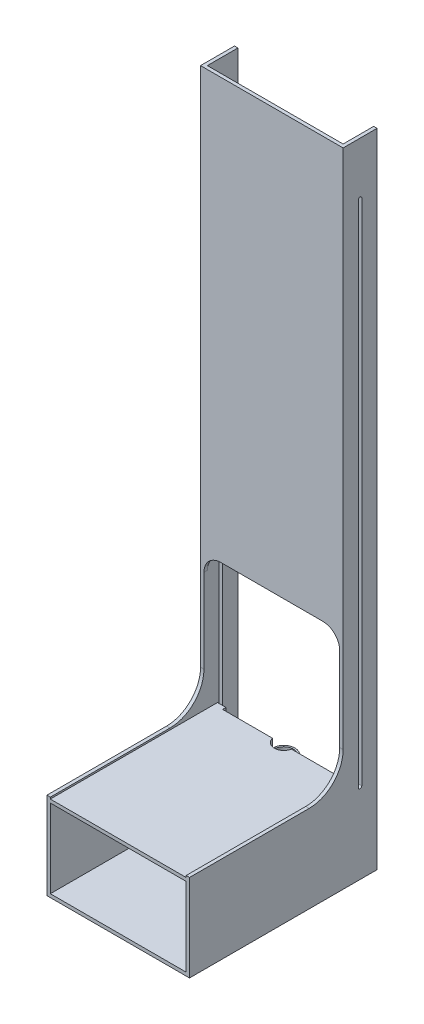
SolidWorks part; units mm, degrees
material "AISI 4340 Steel, annealed"
ref_plane "Front Plane" through (0, 0, 0) normal (0, 0, 1) x (1, 0, 0)
ref_plane "Top Plane" through (0, 0, 0) normal (0, 1, 0) x (1, 0, 0)
ref_plane "Right Plane" through (0, 0, 0) normal (1, 0, 0) x (0, 0, -1)
ref_plane "Right side of elevator platform" through (200, 0, 0) normal (1, 0, 0) x (0, 0, -1)
sketch "Sketch2" plane through (200, 0, 0) normal (1, 0, 0) x (0, 0, -1)
  line L0 (50, 236.5) -> (50, 1736.5) construction
  line L1 (45, 236.5) -> (45, 1736.5)
  line L2 (55, 236.5) -> (55, 1736.5)
  line L4 (0, 0) -> (100, 0)
  line L5 (0, 0) -> (0, 1800)
  line L6 (0, 1800) -> (100, 1800)
  line L7 (100, 0) -> (100, 1800)
  arc A0 (45, 236.5) -> (55, 236.5) centre (50, 236.5) ccw
  arc A1 (55, 1736.5) -> (45, 1736.5) centre (50, 1736.5) ccw
  point P2 (50, 986.5)
  dimension "D6" = 5
  dimension "D1" = 1800
  dimension "D2" = 100
  dimension "D3" = 50
  dimension "D4" = 236.5
  dimension "D5" = 63.5
extrude "Right side guide" add sketch "Sketch2" along normal blind 10
sketch "Sketch3" plane through (200, 0, 0) normal (-1, 0, 0) x (0, 0, 1)
  line L0 (0, 1800) -> (0, 0) construction
  line L1 (-100, 0) -> (0, 0)
  line L2 (-100, 0) -> (-100, 10)
  line L3 (-100, 10) -> (0, 10)
  line L4 (0, 0) -> (0, 10)
  dimension "D1" = 10
extrude "Bottom connection" add sketch "Sketch3" along normal blind 400
sketch "Sketch4" plane through (-200, 0, 0) normal (-1, 0, 0) x (0, 0, 1)
  line L0 (-55, 236.5) -> (-55, 1736.5) construction
  line L1 (-45, 1736.5) -> (-45, 236.5) construction
  line L2 (-55, 236.5) -> (-55, 1736.5)
  line L3 (-45, 1736.5) -> (-45, 236.5)
  line L4 (-100, 10) -> (0, 10)
  line L5 (0, 10) -> (0, 1800)
  line L6 (0, 1800) -> (-100, 1800)
  line L7 (-100, 1800) -> (-100, 10)
  line L9 (0, 10) -> (0, 1800)
  line L10 (0, 1800) -> (-100, 1800)
  line L11 (-100, 1800) -> (-100, 10)
  line L16 (-100, 10) -> (-100, 0)
  line L17 (-100, 0) -> (0, 0)
  line L18 (0, 0) -> (0, 10)
  line L19 (0, 10) -> (-100, 10)
  line L20 (-100, 10) -> (-100, 0)
  line L21 (-100, 0) -> (0, 0)
  line L22 (0, 0) -> (0, 10)
  arc A0 (-45, 1736.5) -> (-55, 1736.5) centre (-50, 1736.5) ccw construction
  arc A1 (-55, 236.5) -> (-45, 236.5) centre (-50, 236.5) ccw construction
  arc A2 (-45, 1736.5) -> (-55, 1736.5) centre (-50, 1736.5) ccw
  arc A3 (-55, 236.5) -> (-45, 236.5) centre (-50, 236.5) ccw
  dimension "D1" = 0
  dimension "D2" = 0
extrude "Left side guide" add sketch "Sketch4" along normal blind 10
sketch "Sketch5" plane through (0, 0, 0) normal (0, 0, 1) x (1, 0, 0)
  line L0 (-200, 10) -> (-200, 1800) construction
  line L1 (-200, 1800) -> (200, 1800)
  line L2 (-200, 1800) -> (-200, 653.8)
  line L3 (-200, 653.8) -> (200, 653.8)
  line L4 (200, 1800) -> (200, 653.8)
  line L5 (200, 1800) -> (200, 10) construction
  line L6 (210, 1800) -> (200, 1800) construction
  line L7 (-200, 10) -> (200, 10) construction
  dimension "D1" = 643.8
extrude "Structural webbing extrude" add sketch "Sketch5" against normal blind 10
sketch "Sketch6" plane through (0, 0, 0) normal (0, 0, 1) x (1, 0, 0)
  line L0 (-210, 251.5) -> (-210, 0)
  line L1 (-210, 0) -> (-210, 1800) construction
  line L2 (-210, 0) -> (210, 0)
  line L3 (210, 0) -> (210, 251.5)
  line L4 (210, 1800) -> (210, 0) construction
  line L5 (210, 251.5) -> (200, 251.5)
  line L6 (200, 653.8) -> (200, 10) construction
  line L7 (200, 251.5) -> (200, 10)
  line L8 (200, 10) -> (-200, 10)
  line L9 (-200, 10) -> (-200, 251.5)
  line L10 (-200, 10) -> (-200, 653.8) construction
  line L11 (-200, 251.5) -> (-210, 251.5)
  dimension "D1" = 241.5
extrude "Input roller holder extrude" add sketch "Sketch6" along normal blind 452.52
sketch "Sketch7" plane through (200, 0, 0) normal (-1, 0, 0) x (0, 0, 1)
  line L0 (0, 653.8) -> (0, 251.5) construction
  line L1 (452.52, 251.5) -> (-40, 251.5)
  line L2 (452.52, 251.5) -> (452.52, 241.5)
  line L3 (452.52, 241.5) -> (-40, 241.5)
  line L4 (-40, 251.5) -> (-40, 241.5)
  dimension "D1" = 40
  dimension "D2" = 10
extrude "Input roller platform" add sketch "Sketch7" along normal up to next
sketch "Sketch8" plane through (0, 251.5, 0) normal (0, 1, 0) x (1, 0, 0)
  line L1 (-210, -452.52) -> (-200, -452.52)
  line L2 (-210, -452.52) -> (-210, 0)
  line L3 (-210, 0) -> (-200, 0)
  line L4 (-200, -452.52) -> (-200, 0)
  line L5 (200, 0) -> (210, 0)
  line L6 (200, 0) -> (200, -452.52)
  line L7 (200, -452.52) -> (210, -452.52)
  line L8 (210, 0) -> (210, -452.52)
extrude "Siding outline" add sketch "Sketch8" along normal blind 5
sketch "Sketch9" plane through (0, 1800, 0) normal (0, 1, 0) x (1, 0, 0)
  line L8 (200, 100) -> (200, 10)
  line L9 (200, 10) -> (-200, 10)
  line L10 (-200, 10) -> (-200, 100)
  line L11 (-200, 100) -> (-210, 100)
  line L12 (-210, 100) -> (-210, 0)
  line L13 (-210, 0) -> (210, 0)
  line L14 (210, 0) -> (210, 100)
  line L15 (210, 100) -> (200, 100)
  line L16 (200, 100) -> (200, 10)
  line L17 (200, 10) -> (-200, 10)
  line L18 (-200, 10) -> (-200, 100)
  line L19 (-200, 100) -> (-210, 100)
  line L20 (-210, 100) -> (-210, 0)
  line L21 (-210, 0) -> (210, 0)
  line L22 (210, 0) -> (210, 100)
  line L23 (210, 100) -> (200, 100)
  dimension "D1" = 0
extrude "Lip to prevent box from falling out" add sketch "Sketch9" along normal blind 91.5
fillet "Vertical section fillets" radius 100 2 edges at (205, 256.5, 0) (-205, 256.5, 0)
fillet "Smaller fillets" radius 50 2 edges at (200, 653.8, -5) (-200, 653.8, -5)
sketch "Sketch11" plane through (0, 0, -40) normal (0, 0, -1) x (-1, 0, 0)
  line L0 (200, 251.5) -> (-200, 251.5) construction
  line L1 (-175, 251.5) -> (175, 251.5)
  line L2 (-175, 251.5) -> (-175, 241.5)
  line L3 (-175, 241.5) -> (175, 241.5)
  line L4 (175, 251.5) -> (175, 241.5)
  line L5 (200, 241.5) -> (-200, 241.5) construction
  line L6 (-200, 251.5) -> (-200, 241.5) construction
  line L7 (200, 251.5) -> (200, 241.5) construction
  dimension "D1" = 25
  dimension "D2" = 25
extrude "Gate spacing cut" cut sketch "Sketch11" against normal blind 10
sketch "Sketch12" plane through (-200, 0, 0) normal (1, 0, 0) x (0, 0, -1)
  line L1 (45, 221.5) -> (40, 221.5)
  line L2 (45, 221.5) -> (45, 10)
  line L3 (45, 10) -> (40, 10)
  line L4 (40, 221.5) -> (40, 10)
  line L5 (100, 1891.5) -> (100, 10) construction
  line L6 (45, 236.5) -> (45, 1736.5) construction
  line L7 (-452.52, 10) -> (100, 10) construction
  line L8 (40, 241.5) -> (-452.52, 241.5) construction
  line L9 (30, 241.5) -> (25, 241.5)
  line L10 (30, 241.5) -> (30, 10)
  line L11 (30, 10) -> (25, 10)
  line L12 (25, 241.5) -> (25, 10)
  point P17 (0, 0)
  point P18 (45, 221.5)
  point P19 (0, 0)
  point P20 (0, 0)
  dimension "D1" = 60
  dimension "D2" = 20
  dimension "D3" = 5
extrude "Gate guide rails" add sketch "Sketch12" along normal up to next
sketch "Sketch13" plane through (0, 0, -45) normal (0, 0, -1) x (-1, 0, 0)
  line L0 (-200, 221.5) -> (200, 221.5) construction
  line L1 (-160, 221.5) -> (160, 221.5)
  line L2 (-160, 221.5) -> (-160, 10)
  line L3 (-160, 10) -> (160, 10)
  line L4 (160, 221.5) -> (160, 10)
  line L5 (200, 10) -> (-200, 10) construction
  line L6 (-200, 10) -> (-200, 1891.5) construction
  point P8 (0, 221.5)
  dimension "D1" = 40
extrude "Gate rod connection cutout" cut sketch "Sketch13" against normal through all
sketch "Sketch14" plane through (0, 10, 0) normal (0, 1, 0) x (1, 0, 0)
  line L0 (160, 45) -> (-160, 25) construction
  circle A0 centre (0, 35) radius 28
  circle A1 centre (0, 35) radius 33
  point P6 (0, 0)
  point P7 (0, 35)
  dimension "D1" = 56
  dimension "D2" = 5
extrude "Spring cup" add sketch "Sketch14" along normal blind 75
sketch "Sketch15" plane through (0, 85, 0) normal (0, 1, 0) x (1, 0, 0)
  line L0 (200, 30) -> (160, 30) construction
  line L1 (32.619, 30) -> (27.55, 30)
  line L3 (32.619, 40) -> (27.55, 40)
  line L5 (-27.55, 40) -> (-32.619, 40)
  line L6 (-27.55, 30) -> (-32.619, 30)
  circle A0 centre (0, 35) radius 28 construction
  arc A1 (27.55, 40) -> (-27.55, 40) centre (0, 35) ccw
  circle A2 centre (0, 35) radius 33 construction
  arc A3 (32.619, 40) -> (-32.619, 40) centre (0, 35) ccw
  arc A4 (-27.55, 30) -> (27.55, 30) centre (0, 35) ccw
  arc A5 (-32.619, 30) -> (32.619, 30) centre (0, 35) ccw
extrude "Spring container extension" add sketch "Sketch15" along normal up to surface (136.5 mm away) up to face at (0, 221.5, -27.5)
sketch "Sketch16" plane through (0, 221.5, 0) normal (0, 1, 0) x (1, 0, 0)
  circle A0 centre (0, 35) radius 28
  arc A1 (27.55, 40) -> (-27.55, 40) centre (0, 35) ccw construction
extrude "Spring hole (can't insert spring without this)" cut sketch "Sketch16" along normal up to surface (30 mm away) up to face at (0, 251.5, 85.63)
sketch "Sketch17" plane through (0, 221.5, 0) normal (0, 1, 0) x (1, 0, 0)
  line L2 (-26.1534, 25) -> (-31.4484, 25)
  line L3 (31.4484, 25) -> (26.1534, 25)
  line L4 (-26.1534, 25) -> (-31.4484, 25)
  line L5 (31.4484, 25) -> (26.1534, 25)
  arc A2 (-31.4484, 25) -> (31.4484, 25) centre (0, 35) ccw
  arc A3 (-26.1534, 25) -> (26.1534, 25) centre (0, 35) ccw
  arc A4 (-31.4484, 25) -> (31.4484, 25) centre (0, 35) ccw
  arc A5 (-26.1534, 25) -> (26.1534, 25) centre (0, 35) ccw
  dimension "D1" = 0
extrude "Container extension to meet with conveyor plate" add sketch "Sketch17" along normal up to next
fillet "Spring holder fillets" radius 10 4 edges at (0, 10, -68) (-31.4484, 231.5, -25) (31.4484, 231.5, -25) (0, 241.5, -2)
